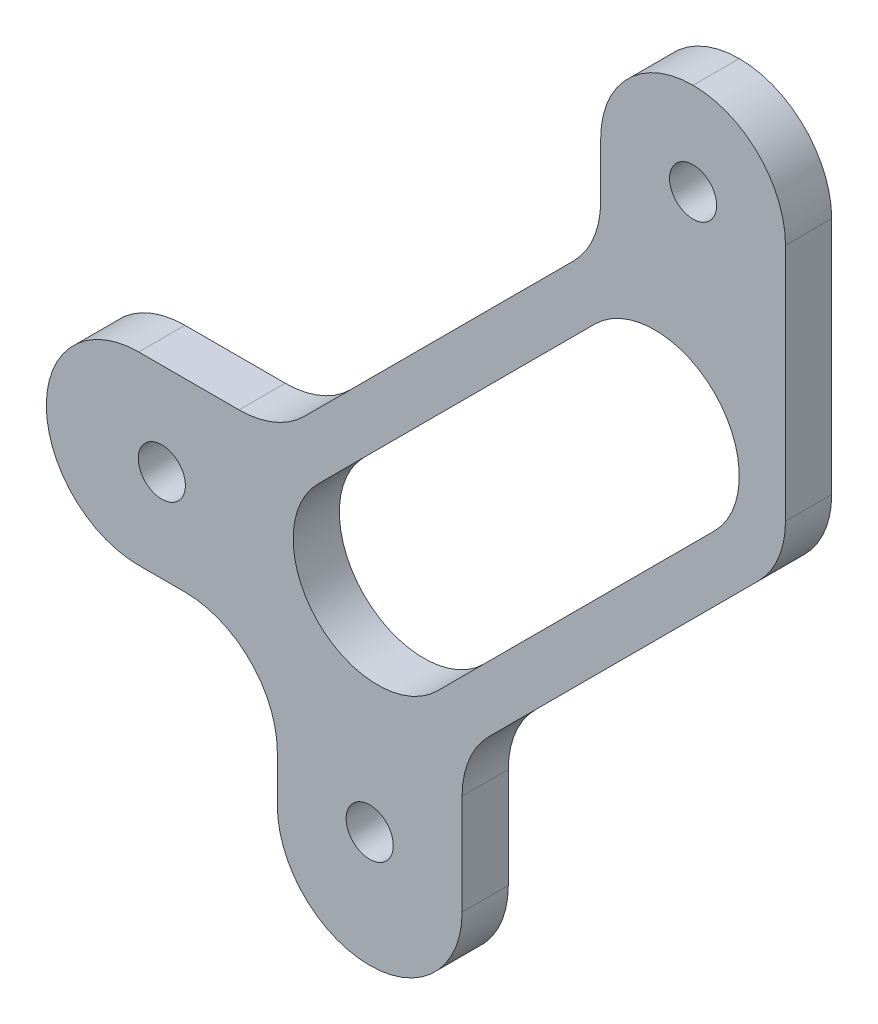
SolidWorks part; units mm, degrees
ref_plane "正面" through (0, 0, 0) normal (0, 0, 1) x (1, 0, 0)
ref_plane "平面" through (0, 0, 0) normal (0, 1, 0) x (1, 0, 0)
ref_plane "右側面" through (0, 0, 0) normal (1, 0, 0) x (0, 0, -1)
sketch "ｽｹｯﾁ1" plane through (0, 0, 0) normal (0, 0, 1) x (1, 0, 0)
  line L0 (0, -25) -> (0, 0)
  line L1 (0, 0) -> (-25, 0)
  line L2 (-25, 0) -> (-25, 20)
  line L3 (-25, 20) -> (0, 20)
  line L4 (0, 20) -> (35, 55)
  line L5 (35, 55) -> (35, 75)
  line L6 (35, 75) -> (55, 75)
  line L7 (55, 75) -> (55, 35)
  line L8 (55, 35) -> (20, 0)
  line L9 (20, 0) -> (20, -25)
  line L10 (20, -25) -> (0, -25)
  line L11 (0, 0) -> (20, 0) construction
  line L12 (-25, 10) -> (30, 10) construction
  line L13 (10, -25) -> (10, 30) construction
  line L14 (45, 75) -> (45, 25) construction
  line L15 (-12.5, 0) -> (-12.5, 20) construction
  line L16 (0, -12.5) -> (20, -12.5) construction
  line L17 (35, 65) -> (55, 65) construction
  circle A0 centre (-12.5, 10) radius 2.55
  circle A1 centre (10, -12.5) radius 2.55
  circle A2 centre (45, 65) radius 2.55
  dimension "D8" = 5.1
  dimension "D1" = 20
  dimension "D2" = 135
  dimension "D3" = 35
  dimension "D4" = 35
  dimension "D5" = 20
  dimension "D6" = 25
  dimension "D7" = 25
extrude "ﾎﾞｽ - 押し出し1" add sketch "ｽｹｯﾁ1" along normal blind 5
fillet "ﾌｨﾚｯﾄ1" radius 10 11 edges at (35, 75, 2.5) (55, 75, 2.5) (20, 0, 2.5) (20, -25, 2.5) (0, -25, 2.5) (0, 0, 2.5) (-25, 0, 2.5) (-25, 20, 2.5) (0, 20, 2.5) (35, 55, 2.5) (55, 35, 2.5)
sketch "ｽｹｯﾁ2" plane through (0, 0, 5) normal (0, 0, 1) x (1, 0, 0)
  line L0 (4.3934, 17.3223) -> (34.3934, 47.3223)
  line L2 (47.3223, 34.3934) -> (17.3223, 4.3934)
  line L4 (22.9289, 2.9289) -> (52.0711, 32.0711) construction
  line L5 (32.0711, 52.0711) -> (2.9289, 22.9289) construction
  line L6 (50, 40.8579) -> (50, 73.6603) construction
  line L7 (55, 39.1421) -> (55, 65) construction
  line L8 (20, 10.8579) -> (20, -5.2804) construction
  line L9 (20, -15) -> (20, -4.1421) construction
  arc A0 (47.3223, 34.3934) -> (34.3934, 47.3223) centre (40.8579, 40.8579) ccw
  arc A1 (4.3934, 17.3223) -> (17.3223, 4.3934) centre (10.8579, 10.8579) ccw
  arc A2 (55, 65) -> (45, 75) centre (45, 65) ccw construction
  dimension "D1" = 5
  dimension "D2" = 5
  dimension "D3" = 5
extrude "ｶｯﾄ - 押し出し1" cut sketch "ｽｹｯﾁ2" against normal through all
